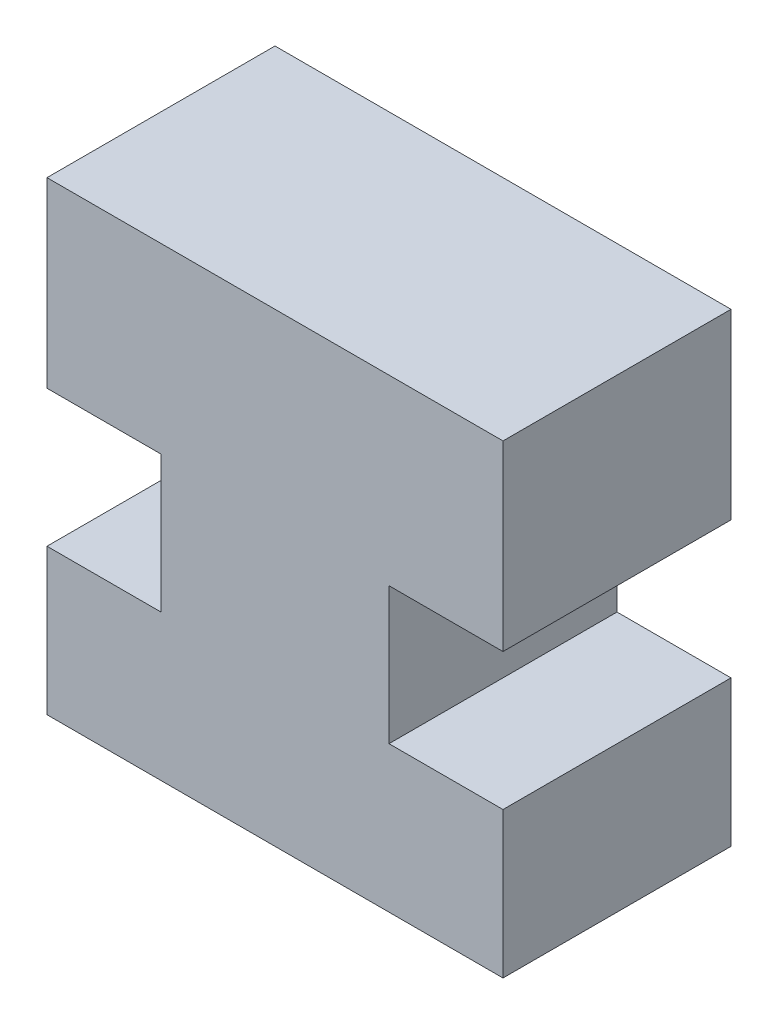
SolidWorks part; units mm, degrees
ref_plane "Front Plane" through (0, 0, 0) normal (0, 0, 1) x (1, 0, 0)
ref_plane "Top Plane" through (0, 0, 0) normal (0, 1, 0) x (1, 0, 0)
ref_plane "Right Plane" through (0, 0, 0) normal (1, 0, 0) x (0, 0, -1)
sketch "Sketch2" plane through (0, 0, 0) normal (0, 0, 1) x (1, 0, 0)
  line L0 (0, 0) -> (12.7, 0)
  line L1 (12.7, 0) -> (12.7, -5.08)
  line L2 (12.7, -5.08) -> (9.525, -5.08)
  line L3 (9.525, -5.08) -> (9.525, -8.89)
  line L4 (9.525, -8.89) -> (12.7, -8.89)
  line L5 (12.7, -8.89) -> (12.7, -12.954)
  line L6 (12.7, -12.954) -> (0, -12.954)
  line L7 (0, -12.954) -> (0, -8.89)
  line L8 (0, -8.89) -> (3.175, -8.89)
  line L9 (3.175, -8.89) -> (3.175, -5.08)
  line L10 (3.175, -5.08) -> (0, -5.08)
  line L11 (0, -5.08) -> (0, 0)
  dimension "D1" = 12.7
  dimension "D2" = 12.7
  dimension "D3" = 5.08
  dimension "D4" = 3.81
  dimension "D5" = 5.08
  dimension "D6" = 3.81
  dimension "D7" = 7.874
  dimension "D8" = 3.175
  dimension "D9" = 3.175
extrude "body" add sketch "Sketch2" along normal blind 6.35
ref_point "centre of flag base"
sketch "Sketch4" plane through (0, -12.954, 0) normal (0, -1, 0) x (1, 0, 0)
  circle A0 centre (6.35, 3.175) radius 1.27
extrude "flag" add sketch "Sketch4" along normal blind 0.254
fillet "holder" radius 2.54 1 edges at (6.35, -12.954, 4.445)
ref_point "centre of flag top"
